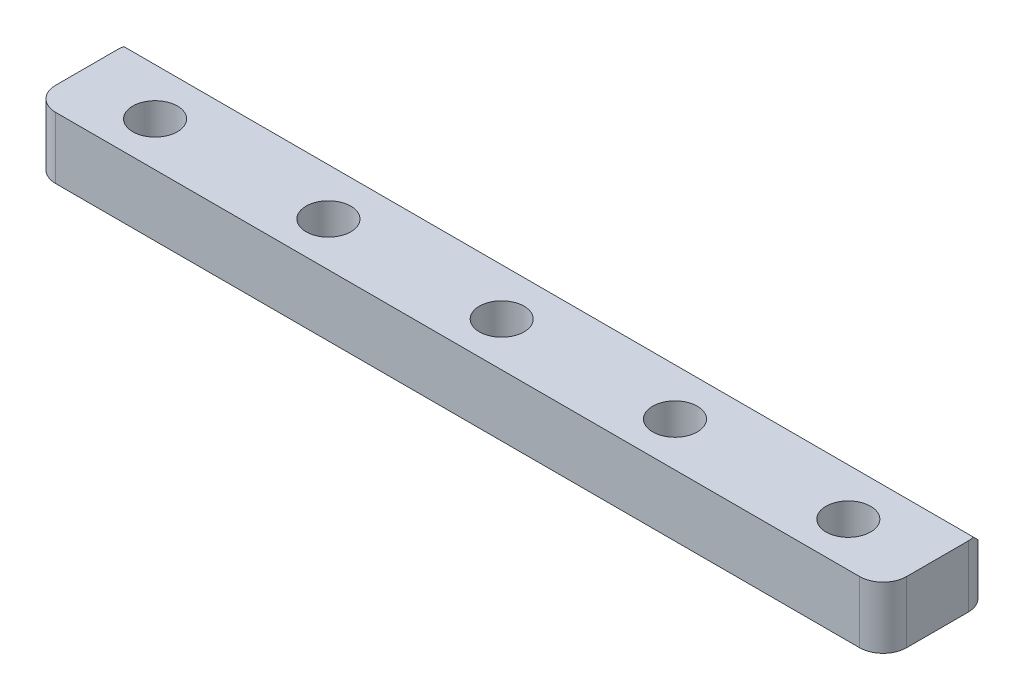
SolidWorks part; units mm, degrees
ref_plane "Alzado" through (0, 0, 0) normal (0, 0, 1) x (1, 0, 0)
ref_plane "Planta" through (0, 0, 0) normal (0, 1, 0) x (1, 0, 0)
ref_plane "Vista lateral" through (0, 0, 0) normal (1, 0, 0) x (0, 0, -1)
sketch "Croquis1" plane through (0, 0, 0) normal (0, 1, 0) x (1, 0, 0)
  line L0 (34.2094, 5.5) -> (-34.2094, 5.5)
  line L2 (-34.2094, -3.75) -> (34.2094, -3.75)
  line L5 (-36.2094, 3.5) -> (-36.2094, -1.75)
  line L8 (36.2094, 3.5) -> (36.2094, -1.75)
  circle A0 centre (29.4981, 0) radius 1.9
  circle A1 centre (14.7481, 0) radius 1.9
  circle A2 centre (0, 0) radius 1.9
  circle A3 centre (-14.7481, 0) radius 1.9
  circle A4 centre (-29.4981, 0) radius 1.9
  arc A5 (34.2094, 5.5) -> (36.2094, 3.5) centre (34.2094, 3.5) cw
  arc A6 (36.2094, -1.75) -> (34.2094, -3.75) centre (34.2094, -1.75) cw
  arc A7 (-34.2094, -3.75) -> (-36.2094, -1.75) centre (-34.2094, -1.75) cw
  arc A8 (-34.2094, 5.5) -> (-36.2094, 3.5) centre (-34.2094, 3.5) ccw
  point P3 (-1.882, -0.2609)
  dimension "D3" = 2
  dimension "D1" = 5.5
  dimension "D2" = 3.75
  dimension "D4" = 0
extrude "Saliente-Extruir1" add sketch "Croquis1" along normal blind 5.25
chamfer "Chaflán1" distance 1.5 angle 45 1 edges at (0, 5.25, -5.5) tangent propagation no
